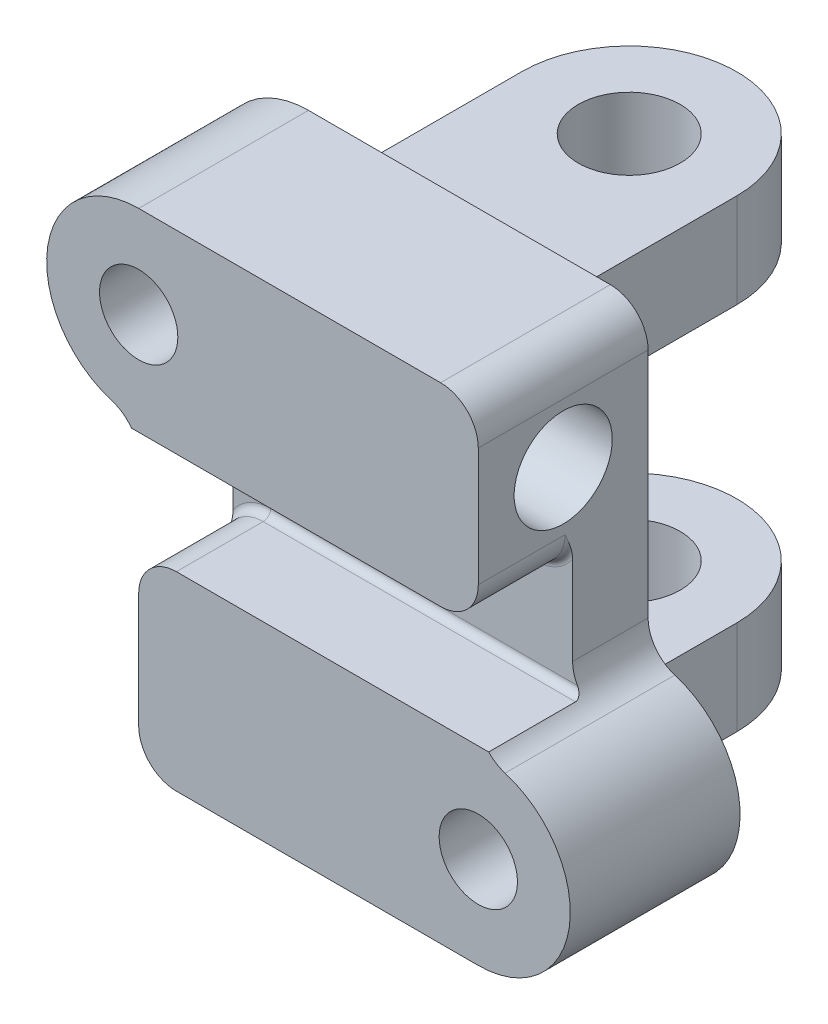
SolidWorks part; units mm, degrees
ref_plane "Front Plane" through (0, 0, 0) normal (0, 0, 1) x (1, 0, 0)
ref_plane "Top Plane" through (0, 0, 0) normal (0, 1, 0) x (1, 0, 0)
ref_plane "Right Plane" through (0, 0, 0) normal (1, 0, 0) x (0, 0, -1)
sketch "Sketch2" plane through (0, 0, 0) normal (0, 1, 0) x (1, 0, 0)
  line L1 (-7.239, 0) -> (-7.239, 10.16)
  line L2 (7.239, 0) -> (7.239, 10.16)
  line L3 (-7.239, 0) -> (7.239, 0)
  arc A1 (7.239, 10.16) -> (-7.239, 10.16) centre (0, 10.16) ccw
  circle A2 centre (0, 10.16) radius 3.429
  point P2 (0, 0)
  dimension "D2" = 6.858
  dimension "D3" = 10.16
  dimension "D1" = 3.81
extrude "Boss-Extrude1" add sketch "Sketch2" along normal blind 6.35
ref_plane "Plane1" through (0, 31.242, 0) normal (0, -1, 0) x (-1, 0, 0)
sketch "Sketch6" plane through (0, 31.242, 0) normal (0, -1, 0) x (-1, 0, 0)
  line L0 (7.239, 0) -> (-7.239, 0) construction
  line L1 (-7.239, 0) -> (-7.239, 10.16) construction
  line L2 (7.239, 10.16) -> (7.239, 0) construction
  line L3 (7.239, 0) -> (-7.239, 0)
  line L4 (-7.239, 0) -> (-7.239, 10.16)
  line L5 (7.239, 10.16) -> (7.239, 0)
  arc A0 (7.239, 10.16) -> (-7.239, 10.16) centre (0, 10.16) ccw construction
  arc A1 (7.239, 10.16) -> (-7.239, 10.16) centre (0, 10.16) ccw
  circle A3 centre (0, 10.16) radius 3.429
  circle A4 centre (0, 10.16) radius 3.429 construction
extrude "Boss-Extrude2" add sketch "Sketch6" along normal blind 6.35 separate body
ref_plane "Plane2" through (0, 15.621, 0) normal (0, -1, 0) x (-1, 0, 0)
sketch "Sketch7" plane through (0, 0, 0) normal (0, 0, 1) x (1, 0, 0)
  line L0 (-7.9629, 15.621) -> (7.9629, 15.621) construction
  line L11 (11.43, -0.7302) -> (-8.89, -0.7302)
  line L12 (-11.43, 1.8098) -> (-11.43, 17.4274)
  line L13 (-11.43, 31.9722) -> (8.89, 31.9722)
  line L14 (11.43, 29.4322) -> (11.43, 13.8146)
  circle A14 centre (-11.43, 25.781) radius 2.6352
  circle A15 centre (11.43, 5.461) radius 2.6352
  arc A18 (-13.2311, 19.8575) -> (-11.43, 31.9722) centre (-11.43, 25.781) cw
  arc A21 (13.2311, 11.3845) -> (11.43, -0.7302) centre (11.43, 5.461) cw
  arc A22 (8.89, 31.9722) -> (11.43, 29.4322) centre (8.89, 29.4322) cw
  arc A23 (-8.89, -0.7302) -> (-11.43, 1.8098) centre (-8.89, 1.8098) cw
  arc A24 (-11.43, 17.4274) -> (-13.2311, 19.8575) centre (-13.97, 17.4274) ccw
  arc A25 (11.43, 13.8146) -> (13.2311, 11.3845) centre (13.97, 13.8146) ccw
  dimension "D1" = 5.2705
  dimension "D2" = 5.2705
  dimension "D3" = 11.43
  dimension "D4" = 11.43
  dimension "D5" = 10.16
  dimension "D7" = 3.556
  dimension "D8" = 3.556
  dimension "D9" = 2.54
  dimension "D6" = 10.16
extrude "Boss-Extrude3" add sketch "Sketch7" along normal blind 11.43
sketch "Sketch11" plane through (0, 0, 11.43) normal (0, 0, 1) x (1, 0, 0)
  line L0 (11.43, 18.923) -> (-11.917, 18.923)
  line L1 (-11.43, 12.065) -> (12.1287, 12.065)
  line L7 (-11.43, 17.4274) -> (-11.43, 1.8098) construction
  line L8 (11.43, 13.8146) -> (11.43, 29.4322) construction
  line L9 (-11.43, 17.4274) -> (-11.43, 12.065)
  line L10 (11.43, 13.8146) -> (11.43, 18.923)
  line L11 (-7.9629, 15.621) -> (7.9629, 15.621) construction
  arc A8 (-11.43, 17.4274) -> (-13.2311, 19.8575) centre (-13.97, 17.4274) ccw construction
  arc A9 (11.43, 13.8146) -> (13.2311, 11.3845) centre (13.97, 13.8146) ccw construction
  arc A10 (-11.43, 17.4274) -> (-11.917, 18.923) centre (-13.97, 17.4274) ccw
  arc A11 (11.43, 13.8146) -> (12.1287, 12.065) centre (13.97, 13.8146) ccw
  dimension "D1" = 6.858
  dimension "D2" = 3.556
extrude "Cut-Extrude2" cut sketch "Sketch11" against normal blind 6.35
fillet "Fillet2" radius 2.54 2 edges at (-11.43, 12.065, 8.255) (11.43, 18.923, 8.255)
fillet "Fillet3" radius 0.508 12 edges at (-7.239, 3.175, 0) (0, 0, 0) (0, 6.35, 0) (7.239, 3.175, 0) (7.239, 28.067, 0) (0, 31.242, 0) (-7.239, 28.067, 0) (0, 24.892, 0) (-10.6861, 11.3211, 5.08) (10.6861, 19.6669, 5.08) (1.6193, 12.065, 5.08) (-1.5135, 18.923, 5.08)
sketch "Sketch12" plane through (11.43, 0, 0) normal (1, 0, 0) x (0, 0, -1)
  line L0 (-11.43, 31.9722) -> (0, 31.9722) construction
  line L1 (-11.43, 21.463) -> (-11.43, 29.4322) construction
  circle A0 centre (-5.715, 25.4476) radius 3.302
  point P4 (-5.715, 31.9722)
  point P7 (-11.43, 25.4476)
  dimension "D1" = 6.604
extrude "Cut-Extrude3" cut sketch "Sketch12" against normal blind 15.875
sketch "Sketch13" plane through (-11.43, 0, 0) normal (-1, 0, 0) x (0, 0, 1)
  line L0 (11.43, -0.7302) -> (0, -0.7302) construction
  line L1 (11.43, 9.525) -> (11.43, 1.8098) construction
  circle A0 centre (5.715, 5.6674) radius 3.302
  point P4 (5.715, -0.7302)
  point P8 (11.43, 5.6674)
  dimension "D1" = 6.604
extrude "Cut-Extrude4" cut sketch "Sketch13" against normal blind 15.875
equation "\"Motor Shaft Diam\"= .1175in"
equation "\"Stroke Length\"=0.5"
equation "\"Binding Post Diam\"= 5 / 16"
